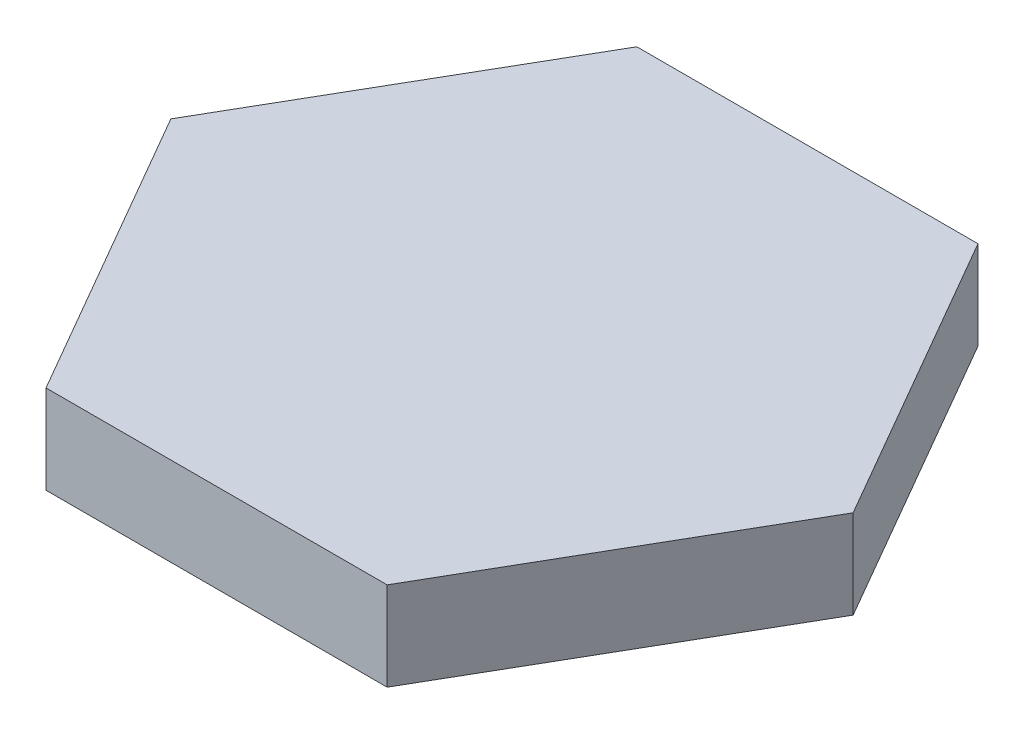
SolidWorks part; units mm, degrees
ref_plane "Front Plane" through (0, 0, 0) normal (0, 0, 1) x (1, 0, 0)
ref_plane "Top Plane" through (0, 0, 0) normal (0, 1, 0) x (1, 0, 0)
ref_plane "Right Plane" through (0, 0, 0) normal (1, 0, 0) x (0, 0, -1)
sketch "Sketch1" plane through (0, 0, 0) normal (0, 1, 0) x (1, 0, 0)
  line L1 (73.3235, 0) -> (36.6617, 63.5)
  line L2 (36.6617, 63.5) -> (-36.6617, 63.5)
  line L3 (-36.6617, 63.5) -> (-73.3235, 0)
  line L4 (-73.3235, 0) -> (-36.6617, -63.5)
  line L5 (-36.6617, -63.5) -> (36.6617, -63.5)
  line L6 (36.6617, -63.5) -> (73.3235, 0)
  circle A0 centre (0, 0) radius 63.5 construction
  dimension "D1" = 127
extrude "Boss-Extrude1" add sketch "Sketch1" along normal blind 19.05
sketch "Sketch3" plane through (0, 0, 0) normal (0, 1, 0) x (1, 0, 0)
  line L1 (38.1, -9.525) -> (-38.1, -9.525)
  line L2 (38.1, -9.525) -> (38.1, -47.625)
  line L3 (38.1, -47.625) -> (-38.1, -47.625)
  line L4 (-38.1, -9.525) -> (-38.1, -47.625)
  line L5 (38.1, -9.525) -> (-38.1, -47.625) construction
  line L6 (38.1, -47.625) -> (-38.1, -9.525) construction
  point P0 (0, -28.575)
  dimension "D1" = 38.1
  dimension "D2" = 76.2
  dimension "D3" = 38.1
  dimension "D4" = 9.525
sketch "Sketch4" plane through (0, 0, 0) normal (0, 1, 0) x (1, 0, 0)
  line L0 (36.6617, 63.5) -> (-36.6617, 63.5) construction
  line L1 (47.625, 31.75) -> (-47.625, 31.75)
  line L2 (47.625, 31.75) -> (47.625, 3.175)
  line L3 (47.625, 3.175) -> (-47.625, 3.175)
  line L4 (-47.625, 31.75) -> (-47.625, 3.175)
  line L5 (47.625, 31.75) -> (-47.625, 3.175) construction
  line L6 (47.625, 3.175) -> (-47.625, 31.75) construction
  point P0 (0, 17.4625)
  dimension "D1" = 95.25
  dimension "D2" = 28.575
  dimension "D3" = 47.625
  dimension "D4" = 31.75
extrude "Cut-Extrude3" cut sketch "Sketch4" along normal blind 6.35
extrude "Cut-Extrude4" cut sketch "Sketch3" along normal blind 12.7
sketch "Sketch6" plane through (0, 0, 0) normal (0, 1, 0) x (1, 0, 0)
  text T0 "<b>Benzene Bots</b>\r\n     Troy, MI" font "Century Gothic" height in points 18
extrude "Cut-Extrude5" cut sketch "Sketch6" along normal blind 3.175
sketch "Sketch8" plane through (0, 0, 0) normal (0, 1, 0) x (1, 0, 0)
  text T0 "Courtesy of Sanket Nayak" font "Century Gothic" height in points 10
extrude "Cut-Extrude6" cut sketch "Sketch8" along normal blind 3.175
